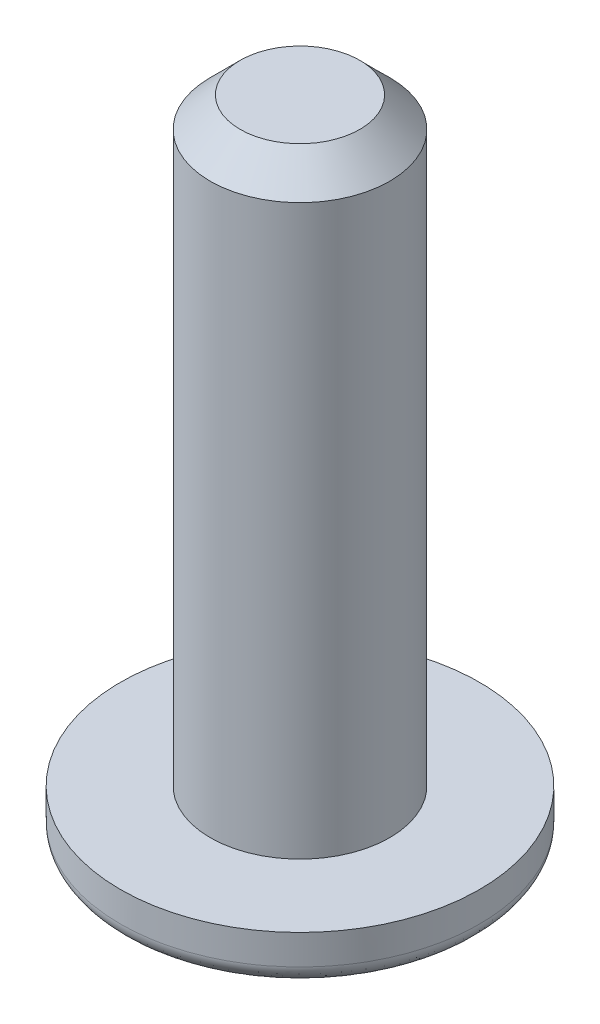
SolidWorks part; units mm, degrees
material "ASTM A36 钢"
ref_plane "前视基准面" through (0, 0, 0) normal (0, 0, 1) x (1, 0, 0)
ref_plane "上视基准面" through (0, 0, 0) normal (0, 1, 0) x (1, 0, 0)
ref_plane "右视基准面" through (0, 0, 0) normal (1, 0, 0) x (0, 0, -1)
sketch "草图1" plane through (0, 0, 0) normal (0, 1, 0) x (1, 0, 0)
  circle A0 centre (0, 0) radius 3
extrude "凸台-拉伸1" add sketch "草图1" along normal blind 1
sketch "草图2" plane through (0, 1, 0) normal (0, 1, 0) x (1, 0, 0)
  circle A0 centre (0, 0) radius 1.5
extrude "凸台-拉伸2" add sketch "草图2" along normal blind 10
sketch "草图3" plane through (0, 0, 0) normal (0, -1, 0) x (1, 0, 0)
  line L1 (0, 1.1547) -> (-1, 0.5774)
  line L2 (-1, 0.5774) -> (-1, -0.5774)
  line L3 (-1, -0.5774) -> (0, -1.1547)
  line L4 (0, -1.1547) -> (1, -0.5774)
  line L5 (1, -0.5774) -> (1, 0.5774)
  line L6 (1, 0.5774) -> (0, 1.1547)
  circle A0 centre (0, 0) radius 1 construction
extrude "切除-拉伸1" cut sketch "草图3" against normal blind 1
fillet "圆角1" radius 0.5 1 edges at (0, 0, 3) second distance 1 first distance on face at (0, 1, 3)
chamfer "倒角1" distance 0.5 angle 45 1 edges at (0, 11, 1.5)
